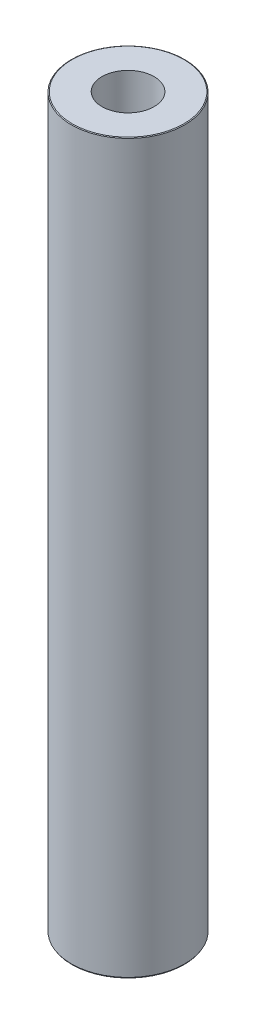
SolidWorks part; units mm, degrees
ref_plane "Front Plane" through (0, 0, 0) normal (0, 0, 1) x (1, 0, 0)
ref_plane "Top Plane" through (0, 0, 0) normal (0, 1, 0) x (1, 0, 0)
ref_plane "Right Plane" through (0, 0, 0) normal (1, 0, 0) x (0, 0, -1)
sketch "Sketch1" plane through (0, 0, 0) normal (0, 1, 0) x (1, 0, 0)
  circle A0 centre (0, 0) radius 27.5
  dimension "SHAFT_OD" = 55
extrude "Boss-Extrude1" add sketch "Sketch1" along normal blind 353.3602
sketch "Sketch2" plane through (0, 0, 0) normal (0, 1, 0) x (1, 0, 0)
  circle A0 centre (0, 0) radius 12.6577
  dimension "BORE_D" = 25.3154
extrude "Cut-Extrude1" cut sketch "Sketch2" along normal through all
chamfer "Chamfer1" distance 0.2462 angle 60 2 edges at (0, 353.3602, 27.5) (0, 0, 27.5) first distance on face at (0, 353.3602, 27.5) first distance on face at (0, 0, 12.6577)
